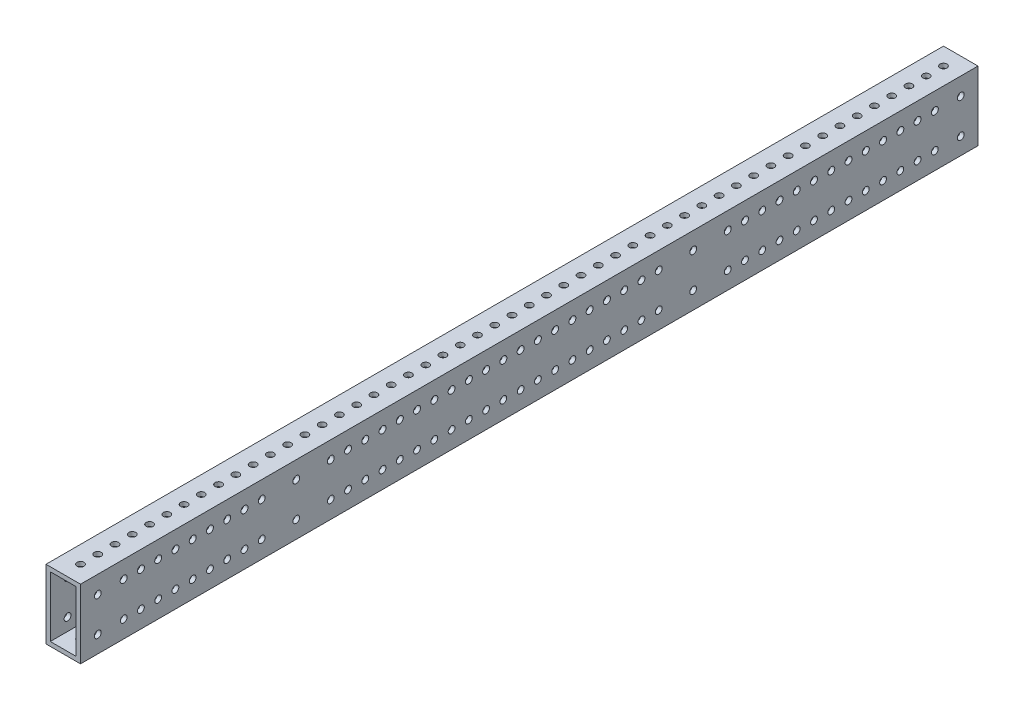
SolidWorks part; units mm, degrees
material "6061-T6 (SS)"
ref_plane "Front Plane" through (0, 0, 0) normal (0, 0, 1) x (1, 0, 0)
ref_plane "Top Plane" through (0, 0, 0) normal (0, 1, 0) x (1, 0, 0)
ref_plane "Right Plane" through (0, 0, 0) normal (1, 0, 0) x (0, 0, -1)
sketch "Sketch1" plane through (0, 0, 0) normal (0, 0, 1) x (1, 0, 0)
  line L0 (-9.525, 22.225) -> (9.525, 22.225)
  line L1 (-12.7, 25.4) -> (12.7, 25.4)
  line L2 (-12.7, 25.4) -> (-12.7, -25.4)
  line L3 (-12.7, -25.4) -> (12.7, -25.4)
  line L4 (12.7, 25.4) -> (12.7, -25.4)
  line L5 (9.525, 22.225) -> (9.525, -22.225)
  line L6 (-9.525, -22.225) -> (9.525, -22.225)
  line L7 (-9.525, 22.225) -> (-9.525, -22.225)
  line L8 (-12.7, 25.4) -> (12.7, -25.4) construction
  line L9 (12.7, 25.4) -> (-12.7, -25.4) construction
  point P5 (0, 0)
  dimension "D1" = 25.4
  dimension "D2" = 50.8
  dimension "D3" = 3.175
extrude "Boss-Extrude1" add sketch "Sketch1" along normal mid plane 660.4
sketch "Sketch2" plane through (0, 25.4, 0) normal (0, 1, 0) x (1, 0, 0)
  line L0 (12.7, -330.2) -> (-12.7, -330.2) construction
  line L1 (-12.7, -330.2) -> (-12.7, 330.2) construction
  line L4 (12.7, 330.2) -> (-12.7, 330.2) construction
  circle A0 centre (0, -317.5) radius 2.5527 construction
  circle A1 centre (25.4, -292.1) radius 2.5527 construction
  circle A2 centre (0, -317.5) radius 2.5527
  circle A3 centre (0, -304.8) radius 2.5527
  circle A4 centre (0, -304.8) radius 2.5527 construction
  circle A5 centre (25.4, -279.4) radius 2.5527 construction
  circle A6 centre (0, -292.1) radius 2.5527
  circle A7 centre (0, -292.1) radius 2.5527 construction
  circle A8 centre (25.4, -266.7) radius 2.5527 construction
  circle A9 centre (0, -279.4) radius 2.5527
  circle A10 centre (0, -279.4) radius 2.5527 construction
  circle A11 centre (25.4, -254) radius 2.5527 construction
  circle A12 centre (0, -266.7) radius 2.5527
  circle A13 centre (0, -266.7) radius 2.5527 construction
  circle A14 centre (25.4, -241.3) radius 2.5527 construction
  circle A15 centre (0, -254) radius 2.5527
  circle A16 centre (0, -254) radius 2.5527 construction
  circle A17 centre (25.4, -228.6) radius 2.5527 construction
  circle A18 centre (0, -241.3) radius 2.5527
  circle A19 centre (0, -241.3) radius 2.5527 construction
  circle A20 centre (25.4, -215.9) radius 2.5527 construction
  circle A21 centre (0, -228.6) radius 2.5527
  circle A22 centre (0, -228.6) radius 2.5527 construction
  circle A23 centre (25.4, -203.2) radius 2.5527 construction
  circle A24 centre (0, -215.9) radius 2.5527
  circle A25 centre (0, -215.9) radius 2.5527 construction
  circle A26 centre (25.4, -190.5) radius 2.5527 construction
  circle A27 centre (0, -203.2) radius 2.5527
  circle A28 centre (0, -203.2) radius 2.5527 construction
  circle A29 centre (25.4, -177.8) radius 2.5527 construction
  circle A30 centre (0, -190.5) radius 2.5527
  circle A31 centre (0, -190.5) radius 2.5527 construction
  circle A32 centre (25.4, -165.1) radius 2.5527 construction
  circle A33 centre (0, -177.8) radius 2.5527
  circle A34 centre (0, -177.8) radius 2.5527 construction
  circle A35 centre (25.4, -152.4) radius 2.5527 construction
  circle A36 centre (0, -165.1) radius 2.5527
  circle A37 centre (0, -165.1) radius 2.5527 construction
  circle A38 centre (25.4, -139.7) radius 2.5527 construction
  circle A39 centre (0, -152.4) radius 2.5527
  circle A40 centre (0, -152.4) radius 2.5527 construction
  circle A41 centre (25.4, -127) radius 2.5527 construction
  circle A42 centre (0, -139.7) radius 2.5527
  circle A43 centre (0, -139.7) radius 2.5527 construction
  circle A44 centre (25.4, -114.3) radius 2.5527 construction
  circle A45 centre (0, -127) radius 2.5527
  circle A46 centre (0, -127) radius 2.5527 construction
  circle A47 centre (25.4, -101.6) radius 2.5527 construction
  circle A48 centre (0, -114.3) radius 2.5527
  circle A49 centre (0, -114.3) radius 2.5527 construction
  circle A50 centre (25.4, -88.9) radius 2.5527 construction
  circle A51 centre (0, -101.6) radius 2.5527
  circle A52 centre (0, -101.6) radius 2.5527 construction
  circle A53 centre (25.4, -76.2) radius 2.5527 construction
  circle A54 centre (0, -88.9) radius 2.5527
  circle A55 centre (0, -88.9) radius 2.5527 construction
  circle A56 centre (25.4, -63.5) radius 2.5527 construction
  circle A57 centre (0, -76.2) radius 2.5527
  circle A58 centre (0, -76.2) radius 2.5527 construction
  circle A59 centre (25.4, -50.8) radius 2.5527 construction
  circle A60 centre (0, -63.5) radius 2.5527
  circle A61 centre (0, -63.5) radius 2.5527 construction
  circle A62 centre (25.4, -38.1) radius 2.5527 construction
  circle A63 centre (0, -50.8) radius 2.5527
  circle A64 centre (0, -50.8) radius 2.5527 construction
  circle A65 centre (25.4, -25.4) radius 2.5527 construction
  circle A66 centre (0, -38.1) radius 2.5527
  circle A67 centre (0, -38.1) radius 2.5527 construction
  circle A68 centre (25.4, -12.7) radius 2.5527 construction
  circle A69 centre (0, -25.4) radius 2.5527
  circle A70 centre (0, -25.4) radius 2.5527 construction
  circle A71 centre (25.4, 0) radius 2.5527 construction
  circle A72 centre (0, -12.7) radius 2.5527
  circle A73 centre (0, -12.7) radius 2.5527 construction
  circle A74 centre (25.4, 12.7) radius 2.5527 construction
  circle A75 centre (0, 0) radius 2.5527
  circle A76 centre (0, 0) radius 2.5527 construction
  circle A77 centre (25.4, 25.4) radius 2.5527 construction
  circle A78 centre (0, 12.7) radius 2.5527
  circle A79 centre (0, 12.7) radius 2.5527 construction
  circle A80 centre (25.4, 38.1) radius 2.5527 construction
  circle A81 centre (0, 25.4) radius 2.5527
  circle A82 centre (0, 25.4) radius 2.5527 construction
  circle A83 centre (25.4, 50.8) radius 2.5527 construction
  circle A84 centre (0, 38.1) radius 2.5527
  circle A85 centre (0, 38.1) radius 2.5527 construction
  circle A86 centre (25.4, 63.5) radius 2.5527 construction
  circle A87 centre (0, 50.8) radius 2.5527
  circle A88 centre (0, 50.8) radius 2.5527 construction
  circle A89 centre (25.4, 76.2) radius 2.5527 construction
  circle A90 centre (0, 63.5) radius 2.5527
  circle A91 centre (0, 63.5) radius 2.5527 construction
  circle A92 centre (25.4, 88.9) radius 2.5527 construction
  circle A93 centre (0, 76.2) radius 2.5527
  circle A94 centre (0, 76.2) radius 2.5527 construction
  circle A95 centre (25.4, 101.6) radius 2.5527 construction
  circle A96 centre (0, 88.9) radius 2.5527
  circle A97 centre (0, 88.9) radius 2.5527 construction
  circle A98 centre (25.4, 114.3) radius 2.5527 construction
  circle A99 centre (0, 101.6) radius 2.5527
  circle A100 centre (0, 101.6) radius 2.5527 construction
  circle A101 centre (25.4, 127) radius 2.5527 construction
  circle A108 centre (0, 127) radius 2.5527 [skipped]
  circle A109 centre (0, 127) radius 2.5527 [skipped]
  circle A110 centre (25.4, 152.4) radius 2.5527 [skipped]
  circle A111 centre (0, 114.3) radius 2.5527 [skipped]
  circle A112 centre (0, 114.3) radius 2.5527 [skipped]
  circle A113 centre (25.4, 139.7) radius 2.5527 [skipped]
  circle A114 centre (25.4, 139.7) radius 2.5527 construction
  circle A115 centre (0, 114.3) radius 2.5527 construction
  circle A116 centre (0, 114.3) radius 2.5527
  circle A117 centre (25.4, 152.4) radius 2.5527 construction
  circle A118 centre (0, 127) radius 2.5527 construction
  circle A119 centre (0, 127) radius 2.5527
  circle A120 centre (25.4, 165.1) radius 2.5527 construction
  circle A121 centre (0, 139.7) radius 2.5527 construction
  circle A122 centre (0, 139.7) radius 2.5527
  circle A123 centre (25.4, 177.8) radius 2.5527 construction
  circle A124 centre (0, 152.4) radius 2.5527 construction
  circle A125 centre (0, 152.4) radius 2.5527
  circle A126 centre (25.4, 190.5) radius 2.5527 construction
  circle A127 centre (0, 165.1) radius 2.5527 construction
  circle A128 centre (0, 165.1) radius 2.5527
  circle A129 centre (25.4, 203.2) radius 2.5527 construction
  circle A130 centre (0, 177.8) radius 2.5527 construction
  circle A131 centre (0, 177.8) radius 2.5527
  circle A132 centre (25.4, 215.9) radius 2.5527 construction
  circle A133 centre (0, 190.5) radius 2.5527 construction
  circle A134 centre (0, 190.5) radius 2.5527
  circle A135 centre (25.4, 228.6) radius 2.5527 construction
  circle A136 centre (0, 203.2) radius 2.5527 construction
  circle A137 centre (0, 203.2) radius 2.5527
  circle A138 centre (25.4, 241.3) radius 2.5527 construction
  circle A139 centre (0, 215.9) radius 2.5527 construction
  circle A140 centre (0, 215.9) radius 2.5527
  circle A141 centre (25.4, 254) radius 2.5527 construction
  circle A142 centre (0, 228.6) radius 2.5527 construction
  circle A143 centre (0, 228.6) radius 2.5527
  circle A144 centre (25.4, 266.7) radius 2.5527 construction
  circle A145 centre (0, 241.3) radius 2.5527 construction
  circle A146 centre (0, 241.3) radius 2.5527
  circle A147 centre (25.4, 279.4) radius 2.5527 construction
  circle A148 centre (0, 254) radius 2.5527 construction
  circle A149 centre (0, 254) radius 2.5527
  circle A150 centre (25.4, 292.1) radius 2.5527 construction
  circle A151 centre (0, 266.7) radius 2.5527 construction
  circle A152 centre (0, 266.7) radius 2.5527
  circle A153 centre (0, 279.4) radius 2.5527
  circle A154 centre (0, 292.1) radius 2.5527
  circle A155 centre (0, 304.8) radius 2.5527
  circle A156 centre (0, 317.5) radius 2.5527
  dimension "D2" = 5.1054
  dimension "D4" = 12.7
  dimension "D9" = 12.7
  dimension "D11" = 12.7
  dimension "D12" = 12.7
  dimension "D1" = 12.7
  dimension "D3" = 12.7
  dimension "D6" = 12.7
  dimension "D7" = 228.6
  dimension "D5" = 36
  dimension "D8" = 14
  dimension "D10" = 5
extrude "Cut-Extrude1" cut sketch "Sketch2" against normal through all
sketch "Sketch4" plane through (12.7, 0, 0) normal (1, 0, 0) x (0, 0, -1)
  line L0 (-330.2, 25.4) -> (330.2, 25.4) construction
  line L1 (-330.2, -25.4) -> (-330.2, 25.4) construction
  line L2 (-330.2, -25.4) -> (330.2, -25.4) construction
  line L3 (-330.2, 25.4) -> (-330.2, -25.4) construction
  line L4 (-159.2701, 25.4) -> (-328.1801, 25.4) construction
  line L5 (-330.2, 25.4) -> (330.2, 25.4) construction
  line L6 (330.2, -25.4) -> (330.2, 25.4) construction
  circle A2 centre (-323.85, -12.7) radius 2.4892 construction
  circle A3 centre (-311.15, -12.7) radius 2.4892 construction
  circle A16 centre (-298.45, -12.7) radius 2.4892
  circle A17 centre (-285.75, -12.7) radius 2.4892
  circle A18 centre (-273.05, -12.7) radius 2.4892
  circle A19 centre (107.95, -12.7) radius 2.4892 construction
  circle A20 centre (120.65, -12.7) radius 2.4892
  circle A21 centre (133.35, -12.7) radius 2.4892 construction
  circle A22 centre (146.05, -12.7) radius 2.4892
  circle A23 centre (158.75, -12.7) radius 2.4892
  circle A24 centre (171.45, -12.7) radius 2.4892
  circle A25 centre (184.15, -12.7) radius 2.4892
  circle A26 centre (196.85, -12.7) radius 2.4892
  circle A27 centre (209.55, -12.7) radius 2.4892
  circle A28 centre (222.25, -12.7) radius 2.4892
  circle A29 centre (234.95, -12.7) radius 2.4892
  circle A30 centre (247.65, -12.7) radius 2.4892
  circle A31 centre (260.35, -12.7) radius 2.4892
  circle A32 centre (273.05, -12.7) radius 2.4892
  circle A33 centre (-323.85, 12.7) radius 2.5527 construction
  circle A34 centre (-311.15, 12.7) radius 2.5527 construction
  circle A35 centre (-260.35, -12.7) radius 2.4892
  circle A36 centre (-247.65, -12.7) radius 2.4892
  circle A37 centre (-234.95, -12.7) radius 2.4892
  circle A38 centre (-222.25, -12.7) radius 2.4892
  circle A39 centre (-209.55, -12.7) radius 2.4892
  circle A40 centre (-196.85, -12.7) radius 2.4892
  circle A41 centre (-184.15, -12.7) radius 2.4892 construction
  circle A42 centre (-171.45, -12.7) radius 2.4892
  circle A43 centre (-158.75, -12.7) radius 2.4892 construction
  circle A44 centre (-146.05, -12.7) radius 2.4892
  circle A45 centre (-133.35, -12.7) radius 2.4892
  circle A46 centre (-120.65, -12.7) radius 2.4892
  circle A47 centre (-107.95, -12.7) radius 2.4892
  circle A48 centre (-95.25, -12.7) radius 2.4892
  circle A49 centre (-82.55, -12.7) radius 2.4892
  circle A50 centre (-69.85, -12.7) radius 2.4892
  circle A51 centre (-57.15, -12.7) radius 2.4892
  circle A52 centre (-44.45, -12.7) radius 2.4892
  circle A53 centre (-31.75, -12.7) radius 2.4892
  circle A54 centre (-19.05, -12.7) radius 2.4892
  circle A55 centre (-6.35, -12.7) radius 2.4892
  circle A56 centre (6.35, -12.7) radius 2.4892
  circle A57 centre (19.05, -12.7) radius 2.4892
  circle A58 centre (31.75, -12.7) radius 2.4892
  circle A59 centre (44.45, -12.7) radius 2.4892
  circle A60 centre (57.15, -12.7) radius 2.4892
  circle A61 centre (69.85, -12.7) radius 2.4892
  circle A62 centre (82.55, -12.7) radius 2.4892
  circle A63 centre (95.25, -12.7) radius 2.4892
  circle A64 centre (-298.45, 12.7) radius 2.5527
  circle A65 centre (-285.75, 12.7) radius 2.5527
  circle A66 centre (-273.05, 12.7) radius 2.5527
  circle A67 centre (-260.35, 12.7) radius 2.5527
  circle A68 centre (-247.65, 12.7) radius 2.5527
  circle A69 centre (-234.95, 12.7) radius 2.5527
  circle A70 centre (-222.25, 12.7) radius 2.5527
  circle A71 centre (-209.55, 12.7) radius 2.5527
  circle A72 centre (-196.85, 12.7) radius 2.5527
  circle A73 centre (-184.15, 12.7) radius 2.5527 construction
  circle A74 centre (-171.45, 12.7) radius 2.5527
  circle A75 centre (-158.75, 12.7) radius 2.5527 construction
  circle A76 centre (-146.05, 12.7) radius 2.5527
  circle A77 centre (-133.35, 12.7) radius 2.5527
  circle A78 centre (-120.65, 12.7) radius 2.5527
  circle A79 centre (-107.95, 12.7) radius 2.5527
  circle A80 centre (-95.25, 12.7) radius 2.5527
  circle A81 centre (-82.55, 12.7) radius 2.5527
  circle A82 centre (-69.85, 12.7) radius 2.5527
  circle A83 centre (-57.15, 12.7) radius 2.5527
  circle A84 centre (-44.45, 12.7) radius 2.5527
  circle A85 centre (-31.75, 12.7) radius 2.5527
  circle A86 centre (-19.05, 12.7) radius 2.5527
  circle A87 centre (-6.35, 12.7) radius 2.5527
  circle A88 centre (6.35, 12.7) radius 2.5527
  circle A89 centre (19.05, 12.7) radius 2.5527
  circle A90 centre (31.75, 12.7) radius 2.5527
  circle A91 centre (44.45, 12.7) radius 2.5527
  circle A92 centre (57.15, 12.7) radius 2.5527
  circle A93 centre (69.85, 12.7) radius 2.5527
  circle A94 centre (82.55, 12.7) radius 2.5527
  circle A95 centre (95.25, 12.7) radius 2.5527
  circle A96 centre (107.95, 12.7) radius 2.5527 construction
  circle A97 centre (120.65, 12.7) radius 2.5527
  circle A98 centre (133.35, 12.7) radius 2.5527 construction
  circle A99 centre (146.05, 12.7) radius 2.5527
  circle A100 centre (158.75, 12.7) radius 2.5527
  circle A101 centre (171.45, 12.7) radius 2.5527
  circle A102 centre (184.15, 12.7) radius 2.5527
  circle A103 centre (196.85, 12.7) radius 2.5527
  circle A104 centre (209.55, 12.7) radius 2.5527
  circle A105 centre (222.25, 12.7) radius 2.5527
  circle A106 centre (234.95, 12.7) radius 2.5527
  circle A107 centre (247.65, 12.7) radius 2.5527
  circle A108 centre (260.35, 12.7) radius 2.5527
  circle A109 centre (273.05, 12.7) radius 2.5527
  circle A110 centre (285.75, 12.7) radius 2.5527
  circle A111 centre (285.75, -12.7) radius 2.4892
  circle A112 centre (298.45, 12.7) radius 2.5527
  circle A113 centre (298.45, -12.7) radius 2.4892
  circle A114 centre (311.15, 12.7) radius 2.5527 construction
  circle A115 centre (311.15, -12.7) radius 2.4892 construction
  circle A116 centre (323.85, 12.7) radius 2.5527 construction
  circle A117 centre (323.85, -12.7) radius 2.4892 construction
  circle A118 centre (-317.5, 12.446) radius 2.5527
  circle A122 centre (-317.5, -12.954) radius 2.5527
  circle A123 centre (317.5, 12.446) radius 2.5527
  circle A124 centre (317.5, -12.954) radius 2.5527
  dimension "D2" = 4.9784
  dimension "D1" = 6.35
  dimension "D8" = 5.1054
  dimension "D9" = 12.7
  dimension "D10" = 6.35
  dimension "D11" = 48
  dimension "D12" = 12.7
  dimension "D13" = 12.7
  dimension "D14" = 12.7
  dimension "D16" = 12.7
  dimension "D17" = 12.954
  dimension "D18" = 5.1054
  dimension "D19" = 12.7
  dimension "D21" = 12.446
  dimension "D22" = 5.1054
  dimension "D23" = 12.954
  dimension "D24" = 12.7
  dimension "D26" = 12.446
  dimension "D3" = 12.7
  dimension "D4" = 12.7
  dimension "D5" = 34
  dimension "D6" = 10
  dimension "D7" = 6
  dimension "D15" = 5
  dimension "D20" = 2
  dimension "D25" = 2
extrude "Cut-Extrude3" cut sketch "Sketch4" against normal through all
